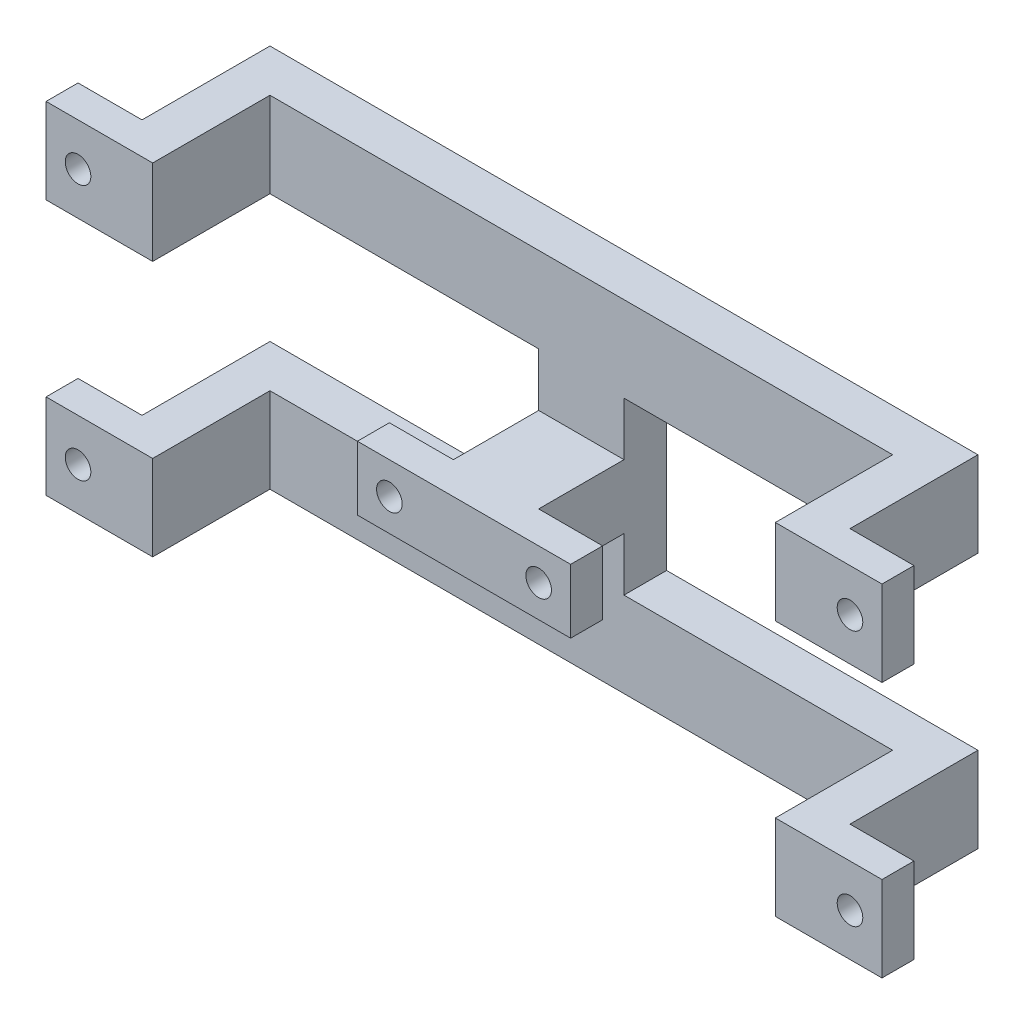
SolidWorks part; units mm, degrees
ref_plane "前视基准面" through (0, 0, 0) normal (0, 0, 1) x (1, 0, 0)
ref_plane "上视基准面" through (0, 0, 0) normal (0, 1, 0) x (1, 0, 0)
ref_plane "右视基准面" through (0, 0, 0) normal (1, 0, 0) x (0, 0, -1)
other "Configuration Table"
sketch "草图1" plane through (0, 0, 0) normal (0, 0, 1) x (1, 0, 0)
  line L0 (-2, 0) -> (2, 0)
  line L1 (-14.6, 8) -> (14.6, 8)
  line L2 (-14.6, 8) -> (-14.6, 4)
  line L3 (-14.6, 4) -> (14.6, 4)
  line L4 (14.6, 8) -> (14.6, 4)
  line L5 (-14.6, -4) -> (14.6, -4)
  line L6 (-14.6, -4) -> (-14.6, -8)
  line L7 (-14.6, -8) -> (14.6, -8)
  line L8 (14.6, -4) -> (14.6, -8)
  line L10 (-2, 4) -> (2, 4)
  line L11 (-2, 4) -> (-2, -4)
  line L12 (-2, -4) -> (2, -4)
  line L13 (2, 4) -> (2, -4)
  line L14 (-14.6, 8) -> (-16.6, 8)
  line L15 (-14.6, 8) -> (-14.6, 4)
  line L16 (-14.6, 4) -> (-16.6, 4)
  line L17 (-16.6, 8) -> (-16.6, 4)
  line L18 (-14.6, -4) -> (-16.6, -4)
  line L19 (-14.6, -4) -> (-14.6, -8)
  line L20 (-14.6, -8) -> (-16.6, -8)
  line L21 (-16.6, -4) -> (-16.6, -8)
  line L22 (14.6, 8) -> (16.6, 8)
  line L23 (14.6, 8) -> (14.6, 4)
  line L24 (14.6, 4) -> (16.6, 4)
  line L25 (16.6, 8) -> (16.6, 4)
  line L26 (14.6, -8) -> (16.6, -8)
  line L27 (14.6, -8) -> (14.6, -4)
  line L28 (14.6, -4) -> (16.6, -4)
  line L29 (16.6, -8) -> (16.6, -4)
  line L30 (-16.6, 8) -> (-19.6, 8)
  line L31 (-16.6, 8) -> (-16.6, 4)
  line L32 (-16.6, 4) -> (-19.6, 4)
  line L33 (-19.6, 8) -> (-19.6, 4)
  line L34 (-16.6, -4) -> (-19.6, -4)
  line L35 (-16.6, -4) -> (-16.6, -8)
  line L36 (-16.6, -8) -> (-19.6, -8)
  line L37 (-19.6, -4) -> (-19.6, -8)
  line L38 (16.6, -8) -> (19.6, -8)
  line L39 (16.6, -8) -> (16.6, -4)
  line L40 (16.6, -4) -> (19.6, -4)
  line L41 (19.6, -8) -> (19.6, -4)
  line L42 (16.6, 4) -> (19.6, 4)
  line L43 (16.6, 4) -> (16.6, 8)
  line L44 (16.6, 8) -> (19.6, 8)
  line L45 (19.6, 4) -> (19.6, 8)
  line L46 (-5, 1.5) -> (5, 1.5)
  line L47 (-5, 1.5) -> (-5, -1.5)
  line L48 (-5, -1.5) -> (5, -1.5)
  line L49 (5, 1.5) -> (5, -1.5)
  circle A3 centre (-3.5, 0) radius 0.6
  circle A4 centre (3.5, 0) radius 0.6
  circle A6 centre (18.1, 6) radius 0.6
  circle A7 centre (18.1, -6) radius 0.6
  circle A8 centre (-18.1, -6) radius 0.6
  circle A9 centre (-18.1, 6) radius 0.6
  point P7 (0, 0)
  point P10 (-2, 0)
  point P11 (0, -4)
  point P18 (0, 8)
  point P43 (0, -1.5)
  point P44 (5, 0)
  point P48 (19.6, -6)
  point P49 (18.1, -8)
  point P50 (-18.1, 4)
  point P51 (-19.6, 6)
  point P57 (3.5, 0.3103)
  dimension "D4" = 4
  dimension "D1" = 4
  dimension "D2" = 8
  dimension "D7" = 1.2
  dimension "D3" = 29.2
  dimension "D5" = 2
  dimension "D6" = 3
  dimension "D8" = 3
  dimension "D9" = 3
  dimension "D10" = 1.5
  dimension "D11" = 1.5
extrude "凸台-拉伸1" add sketch "草图1" along normal blind 2 contours L5 L8 L7 L6 | L3 L4 L1 L2 | L11 L12 L13 L10
extrude "凸台-拉伸2" add sketch "草图1<6>" along normal blind 7.5 contours L26 L29 L28 L8 | L25 L22 L4 L24 | L14 L17 L16 L2 | L18 L21 L20 L6 | L46 L11 L0 L13 | L11 L48 L13 L0 region at (0, 0.75, 0) region at (0, -0.75, 0) region at (-15.6, 6, 0) region at (-15.6, -6, 0) region at (15.6, 6, 0) region at (15.6, -6, 0)
sketch "草图1<6>" plane through (0, 0, 0) normal (0, 0, 1) x (1, 0, 0) same geometry as "草图1"
extrude "凸台-拉伸3" add sketch "草图1<7>" against normal blind 1.5 from surface contours L42 L45 L44 L25 A6 | L38 L41 L40 L29 A7 | L30 L33 L32 L17 A9 | L34 L37 L36 L21 A8 | L47 L48 L11 L46 A3 | L49 L46 L13 L48 A4 region at (-2.0424, -0.75, 0) region at (2.0424, 0.75, 0) region at (-18.1, 4.05, 0) region at (-16.65, -6, 0) region at (16.65, 6, 0) region at (18.1, -4.05, 0) starting at face at (15.6, 6, 7.5)
sketch "草图1<7>" plane through (0, 0, 0) normal (0, 0, 1) x (1, 0, 0) same geometry as "草图1"
